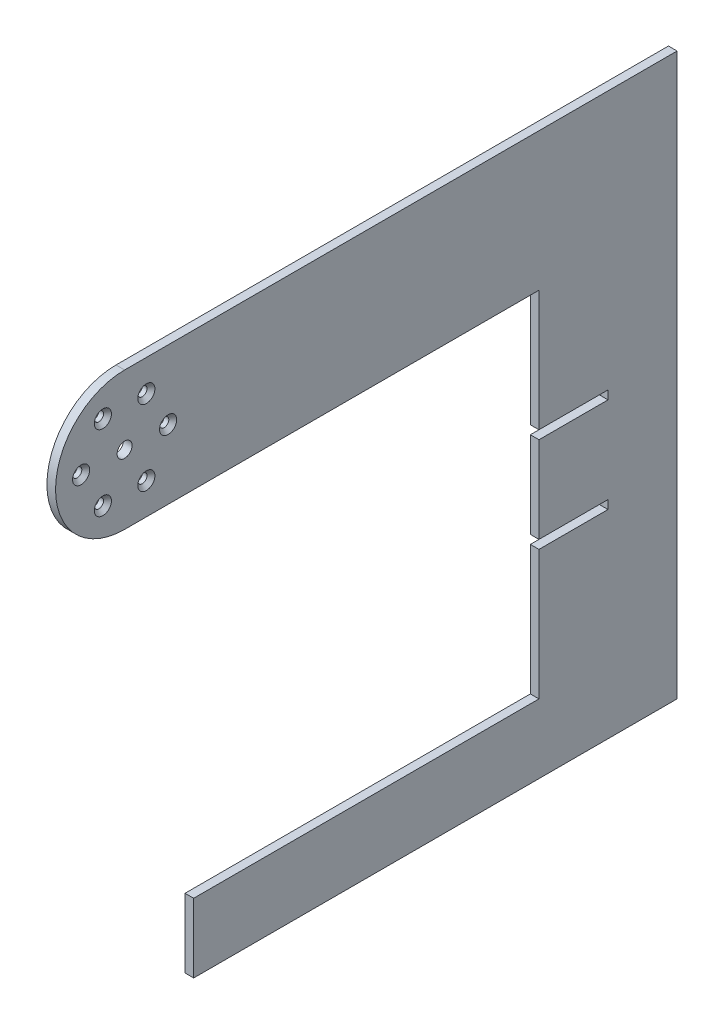
SolidWorks part; units mm, degrees
ref_plane "Front Plane" through (0, 0, 0) normal (0, 0, 1) x (1, 0, 0)
ref_plane "Top Plane" through (0, 0, 0) normal (0, 1, 0) x (1, 0, 0)
ref_plane "Right Plane" through (0, 0, 0) normal (1, 0, 0) x (0, 0, -1)
sketch "Sketch1" plane through (0, 0, 0) normal (1, 0, 0) x (0, 0, -1)
  line L0 (0, -103.1875) -> (0, 103.1875)
  line L1 (0, 103.1875) -> (-203.2, 103.1875)
  line L3 (-203.2, 52.3875) -> (-50.8, 52.3875)
  line L5 (-50.8, -103.1875) -> (0, -103.1875)
  line L6 (-50.8, 52.3875) -> (-50.8, -77.7875)
  line L7 (-50.8, -77.7875) -> (-177.8, -77.7875)
  line L8 (-177.8, -77.7875) -> (-177.8, -103.1875)
  line L9 (-177.8, -103.1875) -> (-50.8, -103.1875)
  arc A0 (-203.2, 103.1875) -> (-203.2, 52.3875) centre (-203.2, 77.7875) ccw
  point P4 (0, 0)
  dimension "D1" = 152.4
  dimension "D2" = 25.4
  dimension "D3" = 50.8
  dimension "D4" = 50.8
  dimension "D5" = 130.175
  dimension "D6" = 127
base flange "Base-Flange1" sketch "Sketch1" thickness 3.175 reverse thickness direction no parameters "D1"=3.175
sketch "Sketch8" plane through (0, 0, 0) normal (1, 0, 0) x (0, 0, -1)
  line L0 (-50.8, 4.7625) -> (-25.4, 4.7625)
  line L2 (-25.4, 4.7625) -> (-25.4, 7.9375)
  line L3 (-25.4, 7.9375) -> (-50.8, 7.9375)
  line L4 (-50.8, 7.9375) -> (-50.8, 4.7625)
  line L5 (-50.8, 7.9375) -> (-50.8, 52.3875) construction
  line L6 (-50.8, -77.7875) -> (-50.8, -30.1625) construction
  line L7 (-50.8, 52.3875) -> (-50.8, -77.7875) construction
  line L8 (-50.8, -26.9875) -> (-25.4, -26.9875)
  line L9 (-25.4, -26.9875) -> (-25.4, -30.1625)
  line L10 (-25.4, -30.1625) -> (-50.8, -30.1625)
  line L11 (-50.8, -30.1625) -> (-50.8, -26.9875)
  dimension "D1" = 25.4
  dimension "D2" = 3.175
  dimension "D3" = 44.45
  dimension "D4" = 47.625
  dimension "D5" = 25.4
  dimension "D6" = 3.175
extrude "Cut-Extrude2" cut sketch "Sketch8" against normal through all normal cut yes
sketch "Sketch11" plane through (0, 0, 0) normal (1, 0, 0) x (0, 0, -1)
  line L0 (-203.2, 103.1875) -> (-203.2, 52.3875) construction
  circle A0 centre (-203.2, 77.7875) radius 2.754
  dimension "D1" = 5.508
extrude "Cut-Extrude4" cut sketch "Sketch11" against normal through all normal cut yes
sketch "Sketch14" plane through (0, 0, 0) normal (1, 0, 0) x (0, 0, -1)
  circle A0 centre (-203.2, 77.7875) radius 16 construction
  point P25 (-219.2, 77.7875)
  point P34 (-211.2, 91.6439)
  point P35 (-195.2, 91.6439)
  point P36 (-187.2, 77.7875)
  point P37 (-195.2, 63.9311)
  point P38 (-211.2, 63.9311)
  dimension "D1" = 32
  dimension "D2" = 6
hole_wizard "CSK for M3 Flat Head Machine Screw1" positions "Sketch14" profile "Sketch13" countersink size "M3" standard "ANSI Metric" end condition through all
sketch "Sketch13" plane through (0, 63.9311, 211.2) normal (0, 1, 0) x (0, 0, -1)
  line L0 (0, 0) -> (0, 3.175)
  line L1 (0, 3.175) -> (1.7, 3.175)
  line L2 (1.7, 3.175) -> (1.7, 1.45)
  line L3 (1.7, 1.45) -> (3.15, 0)
  line L5 (3.15, 0) -> (0, 0)
  line L6 (-1.7, 1.45) -> (-3.15, 0) construction
  line L11 (0, -6.35) -> (0, 107.95) construction
  dimension "Thru Hole Dia." = 3.4
  dimension "Thru Hole Depth" = 3.175
  dimension "Near C'Sink Dia." = 6.3
  dimension "Near C'Sink Angle" = 90
sketch "Bend-Lines1" [suppressed] plane through (0, 0, 0) normal (0, 1, 0) x (1, 0, 0)
sketch "Bounding-Box1" [suppressed] plane through (0, 0, 0) normal (0, 1, 0) x (1, 0, 0)
sheet metal parameters "Sheet-Metal1" thickness 3.175 parameters "D1"=3.175
flat pattern "Flat-Pattern1" [suppressed]
sketch "Bend-Lines2" plane through (0, 0, 0) normal (0, 1, 0) x (1, 0, 0)
sketch3d "Bounding-Box2" [suppressed]
  line L0 (-25.4, 25.4, 0) -> (330.2, 25.4, 0) construction
  line L1 (-25.4, -180.975, 0) -> (330.2, -180.975, 0) construction
  line L2 (-25.4, 25.4, 0) -> (-25.4, -180.975, 0) construction
  line L3 (330.2, 25.4, 0) -> (330.2, -180.975, 0) construction
sheet metal parameters "Sheet-Metal4" thickness 3.175 parameters "D1"=3.175
flat pattern "Flat-Pattern1"
sketch "Bend-Lines2" plane through (0, 0, 0) normal (0, 1, 0) x (1, 0, 0)
sketch3d "Bounding-Box2" [suppressed]
  line L0 (-25.4, 25.4, 0) -> (203.2, 25.4, 0) construction
  line L1 (-25.4, -180.975, 0) -> (203.2, -180.975, 0) construction
  line L2 (-25.4, 25.4, 0) -> (-25.4, -180.975, 0) construction
  line L3 (203.2, 25.4, 0) -> (203.2, -180.975, 0) construction
sheet metal parameters "Sheet-Metal6" thickness 3.175 parameters "D1"=3.175
flat pattern "Flat-Pattern1"
sketch "Bend-Lines2" plane through (0, 0, 0) normal (0, 1, 0) x (1, 0, 0)
sketch3d "Bounding-Box2" [suppressed]
  line L0 (-25.4, 25.4, 0) -> (203.2, 25.4, 0) construction
  line L1 (-25.4, -180.975, 0) -> (203.2, -180.975, 0) construction
  line L2 (-25.4, 25.4, 0) -> (-25.4, -180.975, 0) construction
  line L3 (203.2, 25.4, 0) -> (203.2, -180.975, 0) construction
sheet metal parameters "Sheet-Metal7" thickness 3.175 parameters "D1"=3.175
flat pattern "Flat-Pattern1"
sketch "Bend-Lines2" plane through (0, 0, 0) normal (0, 1, 0) x (1, 0, 0)
sketch3d "Bounding-Box2" [suppressed]
  line L0 (-25.4, 25.4, 0) -> (203.2, 25.4, 0) construction
  line L1 (-25.4, -180.975, 0) -> (203.2, -180.975, 0) construction
  line L2 (-25.4, 25.4, 0) -> (-25.4, -180.975, 0) construction
  line L3 (203.2, 25.4, 0) -> (203.2, -180.975, 0) construction
